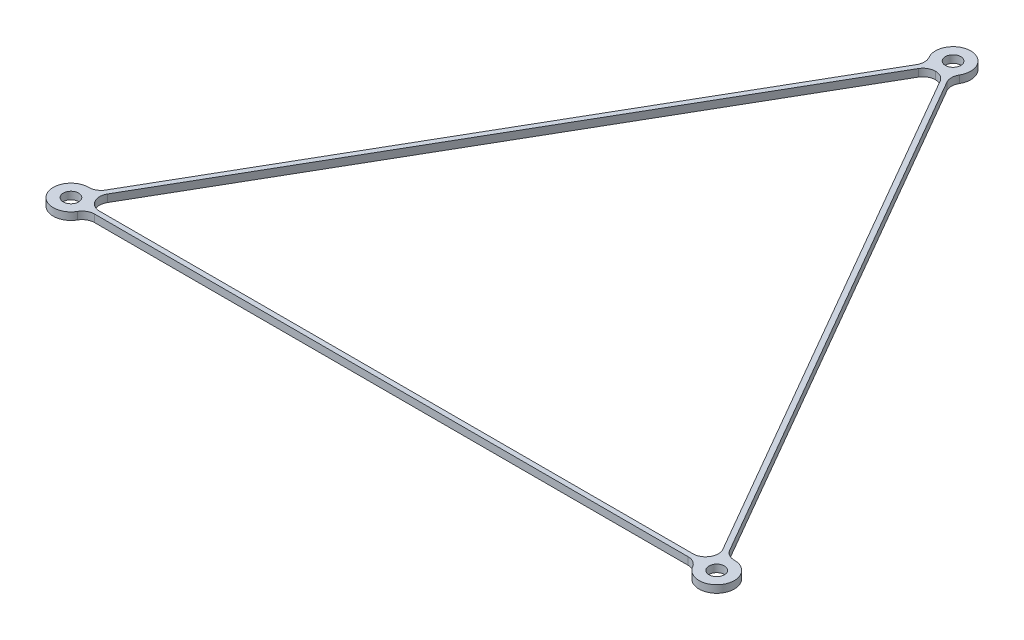
SolidWorks part; units mm, degrees
other "Markup1"
sketch "Sketch1" plane through (0, 0, 0) normal (0.4, 0.515, 0.7581) x (0.8844, 0, -0.4667)
ref_plane "Front Plane" through (0, 0, 0) normal (0, 0, 1) x (1, 0, 0)
ref_plane "Top Plane" through (0, 0, 0) normal (0, 1, 0) x (1, 0, 0)
ref_plane "Right Plane" through (0, 0, 0) normal (1, 0, 0) x (0, 0, -1)
sketch "Sketch2" plane through (0, 0, 0) normal (0, 1, 0) x (1, 0, 0)
  line L0 (65, -37.5278) -> (0, 0) construction
  line L1 (0, 0) -> (0, 75.0555) construction
  line L2 (0, 0) -> (-65, -37.5278) construction
  line L3 (65, -37.5278) -> (-65, -37.5278) construction
  line L4 (-65, -37.5278) -> (0, 75.0555) construction
  line L5 (0, 75.0555) -> (65, -37.5278) construction
  line L6 (-63.6757, -34.234) -> (-2.1903, 72.2618)
  line L7 (63.6757, -34.234) -> (2.1903, 72.2618)
  line L8 (61.4854, -38.0278) -> (-61.4854, -38.0278)
  line L9 (-61.4854, -37.0278) -> (61.4854, -37.0278)
  line L10 (62.8097, -34.734) -> (1.3243, 71.7618)
  line L11 (-1.3243, 71.7618) -> (-62.8097, -34.734)
  line L12 (-32.933, 19.0139) -> (-32.067, 18.5139) construction
  line L13 (0, -38.0278) -> (0, -37.0278) construction
  line L14 (32.933, 19.0139) -> (32.067, 18.5139) construction
  circle A0 centre (0, 75.0555) radius 1.55
  circle A1 centre (65, -37.5278) radius 1.55
  circle A2 centre (-65, -37.5278) radius 1.55
  arc A3 (62.8097, -34.734) -> (61.4854, -37.0278) centre (65, -37.5278) ccw
  arc A4 (-61.4854, -37.0278) -> (-62.8097, -34.734) centre (-65, -37.5278) ccw
  arc A5 (2.1903, 72.2618) -> (-2.1903, 72.2618) centre (0, 75.0555) ccw
  arc A6 (61.4854, -38.0278) -> (63.6757, -34.234) centre (65, -37.5278) ccw
  arc A7 (-63.6757, -34.234) -> (-61.4854, -38.0278) centre (-65, -37.5278) ccw
  arc A8 (-1.3243, 71.7618) -> (1.3243, 71.7618) centre (0, 75.0555) ccw
  point P14 (32.5, 18.7639)
  point P21 (-32.5, 18.7639)
  point P23 (0, -37.5278)
  dimension "D2" = 3.1
  dimension "D3" = 2
  dimension "D1" = 130
  dimension "D4" = 1
extrude "main_shape" add sketch "Sketch2" along normal mid plane 1.5
fillet "outside_fillet" radius 2.5 6 edges at (-2.1903, 0, -72.2618) (2.1903, 0, -72.2618) (63.6757, 0, 34.234) (61.4854, 0, 38.0278) (-61.4854, 0, 38.0278) (-63.6757, 0, 34.234)
fillet "inside_fillet" radius 2.5 6 edges at (-62.8097, 0, 34.734) (-61.4854, 0, 37.0278) (61.4854, 0, 37.0278) (62.8097, 0, 34.734) (1.3243, 0, -71.7618) (-1.3243, 0, -71.7618)
